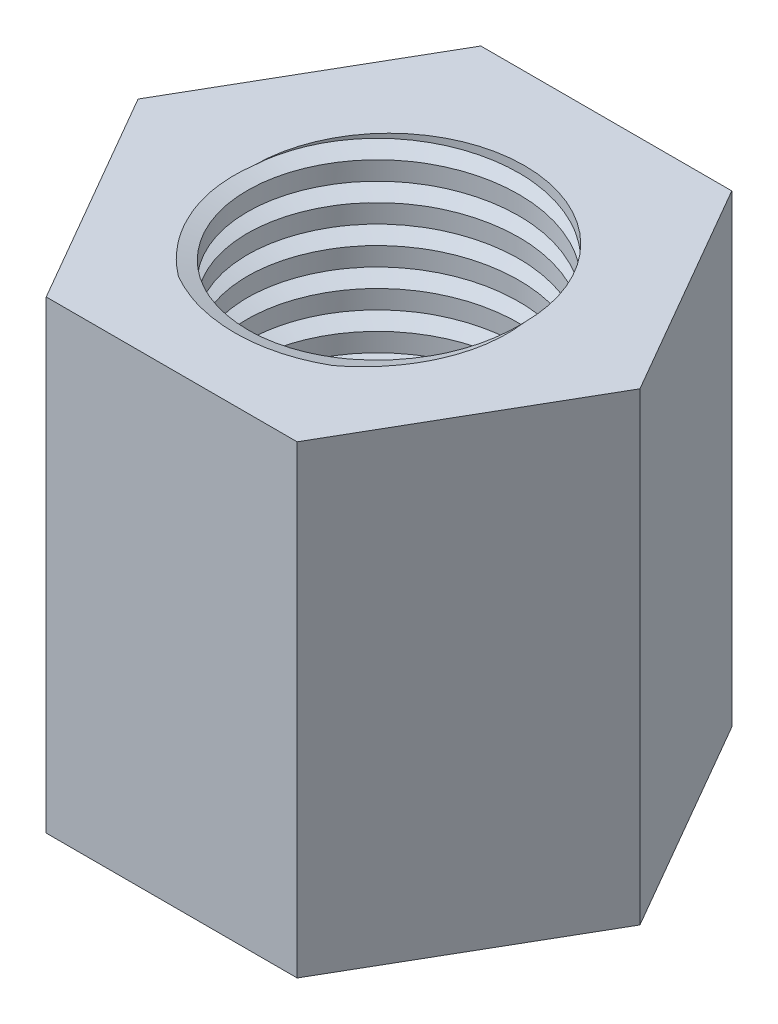
SolidWorks part; units mm, degrees
note: The reader was unsure of these and kept them because the rebuilt part matched: shared geometry of "草图1<3>".
ref_plane "前视基准面" through (0, 0, 0) normal (0, 0, 1) x (1, 0, 0)
ref_plane "上视基准面" through (0, 0, 0) normal (0, 1, 0) x (1, 0, 0)
ref_plane "右视基准面" through (0, 0, 0) normal (1, 0, 0) x (0, 0, -1)
sketch "草图1" plane through (0, 0, 0) normal (0, 1, 0) x (1, 0, 0)
  line L0 (0, 0) -> (0, 4.5761) construction
  line L1 (1.351, -2.34) -> (2.702, 0)
  line L2 (2.702, 0) -> (1.351, 2.34)
  line L3 (1.351, 2.34) -> (-1.351, 2.34)
  line L4 (-1.351, 2.34) -> (-2.702, 0)
  line L5 (-2.702, 0) -> (-1.351, -2.34)
  line L6 (-1.351, -2.34) -> (1.351, -2.34)
  line L7 (0, 4.5761) -> (0, -3.6794) construction
  circle A0 centre (0, 0) radius 2.34 construction
  circle A1 centre (0, 0) radius 1.46
  dimension "D1" = 4.68
  dimension "D2" = 2.92
extrude "凸台-拉伸1" add sketch "草图1" along normal blind 5 contours A1 | L5 L6 L1 L2 L3 L4 A1
extrude "切除-拉伸1" cut sketch "草图1<3>" along normal blind 5 contours A1
sketch "草图1<3>" plane through (0, 0, 0) normal (0, 1, 0) x (1, 0, 0) same geometry as "草图1"
sketch "草图2" plane through (0, 5, 0) normal (0, 1, 0) x (1, 0, 0)
  circle A0 centre (0, 0) radius 1.46
  dimension "D1" = 2.92
ref_plane "基准面1" through (0, 0, 0) normal (0, 0, -1) x (-1, 0, 0)
ref_plane "基准面2" through (0, 5.1, 0) normal (0, 1, 0) x (1, 0, 0)
sketch "草图6" plane through (0, 0, 0) normal (0, -1, 0) x (1, 0, 0)
  circle A0 centre (0, 0) radius 1.46
curve "螺旋线/涡状线2" pitch 0.4 height 9.5 turns 23.75
sketch "草图7" plane through (0, 0, 0) normal (0, 0, -1) x (-1, 0, 0)
  line L0 (1.46, 0.2) -> (1.66, 0.1333)
  line L1 (1.66, 0.0667) -> (1.46, 0)
  line L2 (1.46, 0.2) -> (1.46, 0)
  line L3 (1.66, 0.1333) -> (1.66, 0.0667)
  line L8 (1.351, 0) -> (-1.351, 0) construction
  dimension "D1" = 0.2
  dimension "D3" = 1.46
  dimension "D4" = 0.2
sweep "切除-扫描2" cut profiles "草图7" path "螺旋线/涡状线2"
equation "\"chang\"= 20mm"
equation "\"r\"= 2.92mm"
equation "\"luowengao\"= 6.5mm"
equation "\"rr\"= 4.68mm"
equation "\"D1@草图1\"=\"rr\""
equation "\"D2@草图1\"=\"r\""
equation "\"D1@凸台-拉伸1\"=\"chang\""
equation "\"D1@切除-拉伸1\"=\"luowengao\"+5mm"
equation "\"D1@草图2\"=\"r\""
equation "\"D1@凸台-拉伸2\"=\"luowengao\""
